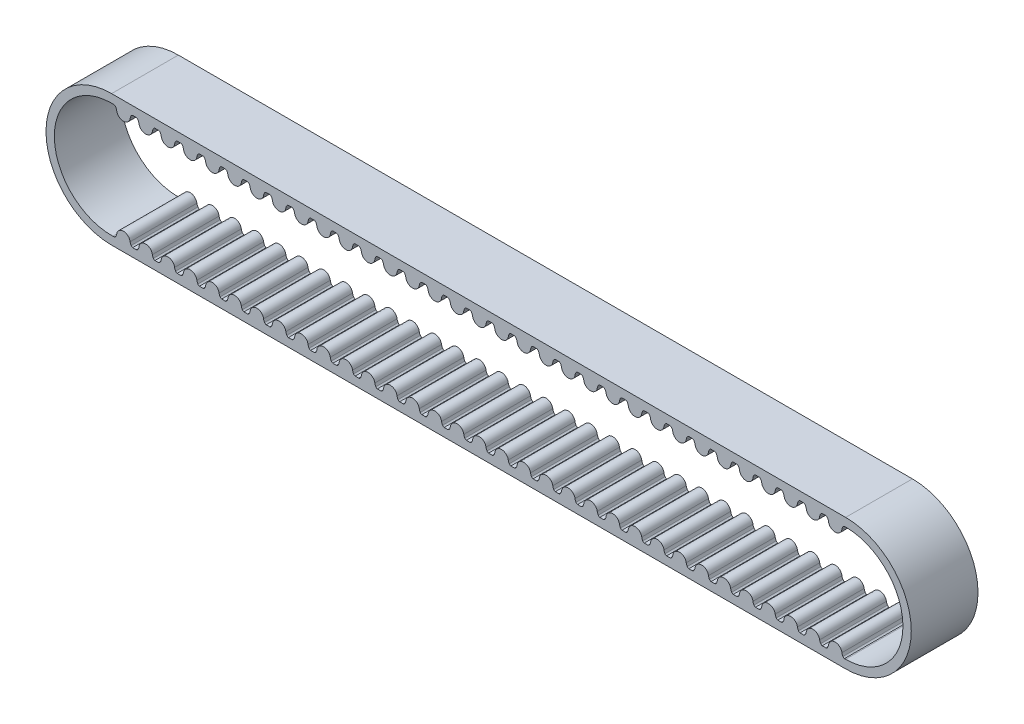
SolidWorks part; units mm, degrees
ref_plane "Front Plane" through (0, 0, 0) normal (0, 0, 1) x (1, 0, 0)
ref_plane "Top Plane" through (0, 0, 0) normal (0, 1, 0) x (1, 0, 0)
ref_plane "Right Plane" through (0, 0, 0) normal (1, 0, 0) x (0, 0, -1)
sketch "Sketch1" plane through (0, 0, 0) normal (0, 0, 1) x (1, 0, 0)
  line L0 (-149.0919, 9.0907) -> (-83.0919, 9.0907)
  line L1 (-148.8622, -1.9593) -> (-148.9877, -1.9593)
  line L2 (-148.8622, -1.9593) -> (-148.8621, -1.9593)
  line L3 (-146.8622, -1.9593) -> (-146.8621, -1.9593)
  line L4 (-147.1989, -1.9593) -> (-146.8622, -1.9593)
  line L5 (-145.1989, -1.9593) -> (-144.8622, -1.9593)
  line L6 (-144.8622, -1.9593) -> (-144.8621, -1.9593)
  line L7 (-143.1989, -1.9593) -> (-142.8622, -1.9593)
  line L8 (-142.8622, -1.9593) -> (-142.8621, -1.9593)
  line L9 (-141.1989, -1.9593) -> (-140.8622, -1.9593)
  line L10 (-140.8622, -1.9593) -> (-140.8621, -1.9593)
  line L11 (-139.1989, -1.9593) -> (-138.8622, -1.9593)
  line L12 (-138.8622, -1.9593) -> (-138.8621, -1.9593)
  line L13 (-137.1989, -1.9593) -> (-136.8622, -1.9593)
  line L14 (-136.8622, -1.9593) -> (-136.8621, -1.9593)
  line L15 (-135.1989, -1.9593) -> (-134.8622, -1.9593)
  line L16 (-134.8622, -1.9593) -> (-134.8621, -1.9593)
  line L17 (-133.1989, -1.9593) -> (-132.8622, -1.9593)
  line L18 (-132.8622, -1.9593) -> (-132.8621, -1.9593)
  line L19 (-131.1989, -1.9593) -> (-130.8622, -1.9593)
  line L20 (-130.8622, -1.9593) -> (-130.8621, -1.9593)
  line L21 (-129.1989, -1.9593) -> (-128.8622, -1.9593)
  line L22 (-128.8622, -1.9593) -> (-128.8621, -1.9593)
  line L23 (-127.1989, -1.9593) -> (-126.8622, -1.9593)
  line L24 (-126.8622, -1.9593) -> (-126.8621, -1.9593)
  line L25 (-125.1989, -1.9593) -> (-124.8622, -1.9593)
  line L26 (-124.8622, -1.9593) -> (-124.8621, -1.9593)
  line L27 (-123.1989, -1.9593) -> (-122.8622, -1.9593)
  line L28 (-122.8622, -1.9593) -> (-122.8621, -1.9593)
  line L29 (-121.1989, -1.9593) -> (-120.8622, -1.9593)
  line L30 (-120.8622, -1.9593) -> (-120.8621, -1.9593)
  line L31 (-119.1989, -1.9593) -> (-118.8622, -1.9593)
  line L32 (-118.8622, -1.9593) -> (-118.8621, -1.9593)
  line L33 (-117.1989, -1.9593) -> (-116.8622, -1.9593)
  line L34 (-116.8622, -1.9593) -> (-116.8621, -1.9593)
  line L35 (-115.1989, -1.9593) -> (-114.8622, -1.9593)
  line L36 (-114.8622, -1.9593) -> (-114.8621, -1.9593)
  line L37 (-113.1989, -1.9593) -> (-112.8622, -1.9593)
  line L38 (-112.8622, -1.9593) -> (-112.8621, -1.9593)
  line L39 (-111.1989, -1.9593) -> (-110.8622, -1.9593)
  line L40 (-110.8622, -1.9593) -> (-110.8621, -1.9593)
  line L41 (-109.1989, -1.9593) -> (-108.8622, -1.9593)
  line L42 (-108.8622, -1.9593) -> (-108.8621, -1.9593)
  line L43 (-107.1989, -1.9593) -> (-106.8622, -1.9593)
  line L44 (-106.8622, -1.9593) -> (-106.8621, -1.9593)
  line L45 (-105.1989, -1.9593) -> (-104.8622, -1.9593)
  line L46 (-104.8622, -1.9593) -> (-104.8621, -1.9593)
  line L47 (-103.1989, -1.9593) -> (-102.8622, -1.9593)
  line L48 (-102.8622, -1.9593) -> (-102.8621, -1.9593)
  line L49 (-101.1989, -1.9593) -> (-100.8622, -1.9593)
  line L50 (-100.8622, -1.9593) -> (-100.8621, -1.9593)
  line L51 (-99.1989, -1.9593) -> (-98.8622, -1.9593)
  line L52 (-98.8622, -1.9593) -> (-98.8621, -1.9593)
  line L53 (-97.1989, -1.9593) -> (-96.8622, -1.9593)
  line L54 (-96.8622, -1.9593) -> (-96.8621, -1.9593)
  line L55 (-95.1989, -1.9593) -> (-94.8622, -1.9593)
  line L56 (-94.8622, -1.9593) -> (-94.8621, -1.9593)
  line L57 (-93.1989, -1.9593) -> (-92.8622, -1.9593)
  line L58 (-92.8622, -1.9593) -> (-92.8621, -1.9593)
  line L59 (-91.1989, -1.9593) -> (-90.8622, -1.9593)
  line L60 (-90.8622, -1.9593) -> (-90.8621, -1.9593)
  line L61 (-89.1989, -1.9593) -> (-88.8622, -1.9593)
  line L62 (-88.8622, -1.9593) -> (-88.8621, -1.9593)
  line L63 (-87.1989, -1.9593) -> (-86.8622, -1.9593)
  line L64 (-86.8622, -1.9593) -> (-86.8621, -1.9593)
  line L65 (-85.1989, -1.9593) -> (-84.8622, -1.9593)
  line L66 (-84.8622, -1.9593) -> (-84.8621, -1.9593)
  line L277 (-83.0919, 3.1907) -> (-46.1296, 3.1907) construction
  line L278 (-83.1989, 8.3407) -> (-83.0919, 8.3407)
  line L279 (-149.0919, -2.7093) -> (-83.0919, -2.7093)
  line L280 (-149.1969, 8.3407) -> (-148.8622, 8.3407)
  line L491 (-84.8622, 8.3407) -> (-84.8621, 8.3407)
  line L492 (-85.1989, 8.3407) -> (-84.8622, 8.3407)
  line L493 (-86.8622, 8.3407) -> (-86.8621, 8.3407)
  line L494 (-87.1989, 8.3407) -> (-86.8622, 8.3407)
  line L495 (-88.8622, 8.3407) -> (-88.8621, 8.3407)
  line L496 (-89.1989, 8.3407) -> (-88.8622, 8.3407)
  line L497 (-90.8622, 8.3407) -> (-90.8621, 8.3407)
  line L498 (-91.1989, 8.3407) -> (-90.8622, 8.3407)
  line L499 (-92.8622, 8.3407) -> (-92.8621, 8.3407)
  line L500 (-93.1989, 8.3407) -> (-92.8622, 8.3407)
  line L501 (-94.8622, 8.3407) -> (-94.8621, 8.3407)
  line L502 (-95.1989, 8.3407) -> (-94.8622, 8.3407)
  line L503 (-96.8622, 8.3407) -> (-96.8621, 8.3407)
  line L504 (-97.1989, 8.3407) -> (-96.8622, 8.3407)
  line L505 (-98.8622, 8.3407) -> (-98.8621, 8.3407)
  line L506 (-99.1989, 8.3407) -> (-98.8622, 8.3407)
  line L507 (-100.8622, 8.3407) -> (-100.8621, 8.3407)
  line L508 (-101.1989, 8.3407) -> (-100.8622, 8.3407)
  line L509 (-102.8622, 8.3407) -> (-102.8621, 8.3407)
  line L510 (-103.1989, 8.3407) -> (-102.8622, 8.3407)
  line L511 (-104.8622, 8.3407) -> (-104.8621, 8.3407)
  line L512 (-105.1989, 8.3407) -> (-104.8622, 8.3407)
  line L513 (-106.8622, 8.3407) -> (-106.8621, 8.3407)
  line L514 (-107.1989, 8.3407) -> (-106.8622, 8.3407)
  line L515 (-108.8622, 8.3407) -> (-108.8621, 8.3407)
  line L516 (-109.1989, 8.3407) -> (-108.8622, 8.3407)
  line L517 (-110.8622, 8.3407) -> (-110.8621, 8.3407)
  line L518 (-111.1989, 8.3407) -> (-110.8622, 8.3407)
  line L519 (-112.8622, 8.3407) -> (-112.8621, 8.3407)
  line L520 (-113.1989, 8.3407) -> (-112.8622, 8.3407)
  line L521 (-114.8622, 8.3407) -> (-114.8621, 8.3407)
  line L522 (-115.1989, 8.3407) -> (-114.8622, 8.3407)
  line L523 (-116.8622, 8.3407) -> (-116.8621, 8.3407)
  line L524 (-117.1989, 8.3407) -> (-116.8622, 8.3407)
  line L525 (-118.8622, 8.3407) -> (-118.8621, 8.3407)
  line L526 (-119.1989, 8.3407) -> (-118.8622, 8.3407)
  line L527 (-120.8622, 8.3407) -> (-120.8621, 8.3407)
  line L528 (-121.1989, 8.3407) -> (-120.8622, 8.3407)
  line L529 (-122.8622, 8.3407) -> (-122.8621, 8.3407)
  line L530 (-123.1989, 8.3407) -> (-122.8622, 8.3407)
  line L531 (-124.8622, 8.3407) -> (-124.8621, 8.3407)
  line L532 (-125.1989, 8.3407) -> (-124.8622, 8.3407)
  line L533 (-126.8622, 8.3407) -> (-126.8621, 8.3407)
  line L534 (-127.1989, 8.3407) -> (-126.8622, 8.3407)
  line L535 (-128.8622, 8.3407) -> (-128.8621, 8.3407)
  line L536 (-129.1989, 8.3407) -> (-128.8622, 8.3407)
  line L537 (-130.8622, 8.3407) -> (-130.8621, 8.3407)
  line L538 (-131.1989, 8.3407) -> (-130.8622, 8.3407)
  line L539 (-132.8622, 8.3407) -> (-132.8621, 8.3407)
  line L540 (-133.1989, 8.3407) -> (-132.8622, 8.3407)
  line L541 (-134.8622, 8.3407) -> (-134.8621, 8.3407)
  line L542 (-135.1989, 8.3407) -> (-134.8622, 8.3407)
  line L543 (-136.8622, 8.3407) -> (-136.8621, 8.3407)
  line L544 (-137.1989, 8.3407) -> (-136.8622, 8.3407)
  line L545 (-138.8622, 8.3407) -> (-138.8621, 8.3407)
  line L546 (-139.1989, 8.3407) -> (-138.8622, 8.3407)
  line L547 (-140.8622, 8.3407) -> (-140.8621, 8.3407)
  line L548 (-141.1989, 8.3407) -> (-140.8622, 8.3407)
  line L549 (-142.8622, 8.3407) -> (-142.8621, 8.3407)
  line L550 (-143.1989, 8.3407) -> (-142.8622, 8.3407)
  line L551 (-144.8622, 8.3407) -> (-144.8621, 8.3407)
  line L552 (-145.1989, 8.3407) -> (-144.8622, 8.3407)
  line L553 (-147.1989, 8.3407) -> (-146.8622, 8.3407)
  line L554 (-146.8622, 8.3407) -> (-146.8621, 8.3407)
  line L555 (-148.8622, 8.3407) -> (-148.8621, 8.3407)
  line L556 (-83.1989, -1.9593) -> (-83.0919, -1.9593)
  arc A0 (-149.1969, 8.3407) -> (-148.9869, -1.9593) centre (-149.0919, 3.1907) ccw
  arc A1 (-83.0919, -1.9593) -> (-83.0919, 8.3407) centre (-83.0919, 3.1907) ccw
  arc A2 (-146.8621, -1.9593) -> (-146.7228, -1.8564) centre (-146.9197, -1.7354) ccw
  arc A3 (-148.8621, -1.9593) -> (-148.7228, -1.8564) centre (-148.9197, -1.7354) ccw
  arc A4 (-148.7228, -1.8564) -> (-148.6336, -1.611) centre (-149.2769, -1.5162) ccw
  arc A5 (-147.4274, -1.611) -> (-148.6336, -1.611) centre (-148.0305, -1.6999) ccw
  arc A6 (-147.4274, -1.611) -> (-147.3383, -1.8564) centre (-146.7842, -1.5162) ccw
  arc A7 (-147.3383, -1.8564) -> (-147.1989, -1.9593) centre (-147.1413, -1.7354) ccw
  arc A8 (-146.7228, -1.8564) -> (-146.6336, -1.611) centre (-147.2769, -1.5162) ccw
  arc A9 (-145.4274, -1.611) -> (-146.6336, -1.611) centre (-146.0305, -1.6999) ccw
  arc A10 (-145.4274, -1.611) -> (-145.3383, -1.8564) centre (-144.7842, -1.5162) ccw
  arc A11 (-145.3383, -1.8564) -> (-145.1989, -1.9593) centre (-145.1413, -1.7354) ccw
  arc A12 (-144.8621, -1.9593) -> (-144.7228, -1.8564) centre (-144.9197, -1.7354) ccw
  arc A13 (-144.7228, -1.8564) -> (-144.6336, -1.611) centre (-145.2769, -1.5162) ccw
  arc A14 (-143.4274, -1.611) -> (-144.6336, -1.611) centre (-144.0305, -1.6999) ccw
  arc A15 (-143.4274, -1.611) -> (-143.3383, -1.8564) centre (-142.7842, -1.5162) ccw
  arc A16 (-143.3383, -1.8564) -> (-143.1989, -1.9593) centre (-143.1413, -1.7354) ccw
  arc A17 (-142.8621, -1.9593) -> (-142.7228, -1.8564) centre (-142.9197, -1.7354) ccw
  arc A18 (-142.7228, -1.8564) -> (-142.6336, -1.611) centre (-143.2769, -1.5162) ccw
  arc A19 (-141.4274, -1.611) -> (-142.6336, -1.611) centre (-142.0305, -1.6999) ccw
  arc A20 (-141.4274, -1.611) -> (-141.3383, -1.8564) centre (-140.7842, -1.5162) ccw
  arc A21 (-141.3383, -1.8564) -> (-141.1989, -1.9593) centre (-141.1413, -1.7354) ccw
  arc A22 (-140.8621, -1.9593) -> (-140.7228, -1.8564) centre (-140.9197, -1.7354) ccw
  arc A23 (-140.7228, -1.8564) -> (-140.6336, -1.611) centre (-141.2769, -1.5162) ccw
  arc A24 (-139.4274, -1.611) -> (-140.6336, -1.611) centre (-140.0305, -1.6999) ccw
  arc A25 (-139.4274, -1.611) -> (-139.3383, -1.8564) centre (-138.7842, -1.5162) ccw
  arc A26 (-139.3383, -1.8564) -> (-139.1989, -1.9593) centre (-139.1413, -1.7354) ccw
  arc A27 (-138.8621, -1.9593) -> (-138.7228, -1.8564) centre (-138.9197, -1.7354) ccw
  arc A28 (-138.7228, -1.8564) -> (-138.6336, -1.611) centre (-139.2769, -1.5162) ccw
  arc A29 (-137.4274, -1.611) -> (-138.6336, -1.611) centre (-138.0305, -1.6999) ccw
  arc A30 (-137.4274, -1.611) -> (-137.3383, -1.8564) centre (-136.7842, -1.5162) ccw
  arc A31 (-137.3383, -1.8564) -> (-137.1989, -1.9593) centre (-137.1413, -1.7354) ccw
  arc A32 (-136.8621, -1.9593) -> (-136.7228, -1.8564) centre (-136.9197, -1.7354) ccw
  arc A33 (-136.7228, -1.8564) -> (-136.6336, -1.611) centre (-137.2769, -1.5162) ccw
  arc A34 (-135.4274, -1.611) -> (-136.6336, -1.611) centre (-136.0305, -1.6999) ccw
  arc A35 (-135.4274, -1.611) -> (-135.3383, -1.8564) centre (-134.7842, -1.5162) ccw
  arc A36 (-135.3383, -1.8564) -> (-135.1989, -1.9593) centre (-135.1413, -1.7354) ccw
  arc A37 (-134.8621, -1.9593) -> (-134.7228, -1.8564) centre (-134.9197, -1.7354) ccw
  arc A38 (-134.7228, -1.8564) -> (-134.6336, -1.611) centre (-135.2769, -1.5162) ccw
  arc A39 (-133.4274, -1.611) -> (-134.6336, -1.611) centre (-134.0305, -1.6999) ccw
  arc A40 (-133.4274, -1.611) -> (-133.3383, -1.8564) centre (-132.7842, -1.5162) ccw
  arc A41 (-133.3383, -1.8564) -> (-133.1989, -1.9593) centre (-133.1413, -1.7354) ccw
  arc A42 (-132.8621, -1.9593) -> (-132.7228, -1.8564) centre (-132.9197, -1.7354) ccw
  arc A43 (-132.7228, -1.8564) -> (-132.6336, -1.611) centre (-133.2769, -1.5162) ccw
  arc A44 (-131.4274, -1.611) -> (-132.6336, -1.611) centre (-132.0305, -1.6999) ccw
  arc A45 (-131.4274, -1.611) -> (-131.3383, -1.8564) centre (-130.7842, -1.5162) ccw
  arc A46 (-131.3383, -1.8564) -> (-131.1989, -1.9593) centre (-131.1413, -1.7354) ccw
  arc A47 (-130.8621, -1.9593) -> (-130.7228, -1.8564) centre (-130.9197, -1.7354) ccw
  arc A48 (-130.7228, -1.8564) -> (-130.6336, -1.611) centre (-131.2769, -1.5162) ccw
  arc A49 (-129.4274, -1.611) -> (-130.6336, -1.611) centre (-130.0305, -1.6999) ccw
  arc A50 (-129.4274, -1.611) -> (-129.3383, -1.8564) centre (-128.7842, -1.5162) ccw
  arc A51 (-129.3383, -1.8564) -> (-129.1989, -1.9593) centre (-129.1413, -1.7354) ccw
  arc A52 (-128.8621, -1.9593) -> (-128.7228, -1.8564) centre (-128.9197, -1.7354) ccw
  arc A53 (-128.7228, -1.8564) -> (-128.6336, -1.611) centre (-129.2769, -1.5162) ccw
  arc A54 (-127.4274, -1.611) -> (-128.6336, -1.611) centre (-128.0305, -1.6999) ccw
  arc A55 (-127.4274, -1.611) -> (-127.3383, -1.8564) centre (-126.7842, -1.5162) ccw
  arc A56 (-127.3383, -1.8564) -> (-127.1989, -1.9593) centre (-127.1413, -1.7354) ccw
  arc A57 (-126.8621, -1.9593) -> (-126.7228, -1.8564) centre (-126.9197, -1.7354) ccw
  arc A58 (-126.7228, -1.8564) -> (-126.6336, -1.611) centre (-127.2769, -1.5162) ccw
  arc A59 (-125.4274, -1.611) -> (-126.6336, -1.611) centre (-126.0305, -1.6999) ccw
  arc A60 (-125.4274, -1.611) -> (-125.3383, -1.8564) centre (-124.7842, -1.5162) ccw
  arc A61 (-125.3383, -1.8564) -> (-125.1989, -1.9593) centre (-125.1413, -1.7354) ccw
  arc A62 (-124.8621, -1.9593) -> (-124.7228, -1.8564) centre (-124.9197, -1.7354) ccw
  arc A63 (-124.7228, -1.8564) -> (-124.6336, -1.611) centre (-125.2769, -1.5162) ccw
  arc A64 (-123.4274, -1.611) -> (-124.6336, -1.611) centre (-124.0305, -1.6999) ccw
  arc A65 (-123.4274, -1.611) -> (-123.3383, -1.8564) centre (-122.7842, -1.5162) ccw
  arc A66 (-123.3383, -1.8564) -> (-123.1989, -1.9593) centre (-123.1413, -1.7354) ccw
  arc A67 (-122.8621, -1.9593) -> (-122.7228, -1.8564) centre (-122.9197, -1.7354) ccw
  arc A68 (-122.7228, -1.8564) -> (-122.6336, -1.611) centre (-123.2769, -1.5162) ccw
  arc A69 (-121.4274, -1.611) -> (-122.6336, -1.611) centre (-122.0305, -1.6999) ccw
  arc A70 (-121.4274, -1.611) -> (-121.3383, -1.8564) centre (-120.7842, -1.5162) ccw
  arc A71 (-121.3383, -1.8564) -> (-121.1989, -1.9593) centre (-121.1413, -1.7354) ccw
  arc A72 (-120.8621, -1.9593) -> (-120.7228, -1.8564) centre (-120.9197, -1.7354) ccw
  arc A73 (-120.7228, -1.8564) -> (-120.6336, -1.611) centre (-121.2769, -1.5162) ccw
  arc A74 (-119.4274, -1.611) -> (-120.6336, -1.611) centre (-120.0305, -1.6999) ccw
  arc A75 (-119.4274, -1.611) -> (-119.3383, -1.8564) centre (-118.7842, -1.5162) ccw
  arc A76 (-119.3383, -1.8564) -> (-119.1989, -1.9593) centre (-119.1413, -1.7354) ccw
  arc A77 (-118.8621, -1.9593) -> (-118.7228, -1.8564) centre (-118.9197, -1.7354) ccw
  arc A78 (-118.7228, -1.8564) -> (-118.6336, -1.611) centre (-119.2769, -1.5162) ccw
  arc A79 (-117.4274, -1.611) -> (-118.6336, -1.611) centre (-118.0305, -1.6999) ccw
  arc A80 (-117.4274, -1.611) -> (-117.3383, -1.8564) centre (-116.7842, -1.5162) ccw
  arc A81 (-117.3383, -1.8564) -> (-117.1989, -1.9593) centre (-117.1413, -1.7354) ccw
  arc A82 (-116.8621, -1.9593) -> (-116.7228, -1.8564) centre (-116.9197, -1.7354) ccw
  arc A83 (-116.7228, -1.8564) -> (-116.6336, -1.611) centre (-117.2769, -1.5162) ccw
  arc A84 (-115.4274, -1.611) -> (-116.6336, -1.611) centre (-116.0305, -1.6999) ccw
  arc A85 (-115.4274, -1.611) -> (-115.3383, -1.8564) centre (-114.7842, -1.5162) ccw
  arc A86 (-115.3383, -1.8564) -> (-115.1989, -1.9593) centre (-115.1413, -1.7354) ccw
  arc A87 (-114.8621, -1.9593) -> (-114.7228, -1.8564) centre (-114.9197, -1.7354) ccw
  arc A88 (-114.7228, -1.8564) -> (-114.6336, -1.611) centre (-115.2769, -1.5162) ccw
  arc A89 (-113.4274, -1.611) -> (-114.6336, -1.611) centre (-114.0305, -1.6999) ccw
  arc A90 (-113.4274, -1.611) -> (-113.3383, -1.8564) centre (-112.7842, -1.5162) ccw
  arc A91 (-113.3383, -1.8564) -> (-113.1989, -1.9593) centre (-113.1413, -1.7354) ccw
  arc A92 (-112.8621, -1.9593) -> (-112.7228, -1.8564) centre (-112.9197, -1.7354) ccw
  arc A93 (-112.7228, -1.8564) -> (-112.6336, -1.611) centre (-113.2769, -1.5162) ccw
  arc A94 (-111.4274, -1.611) -> (-112.6336, -1.611) centre (-112.0305, -1.6999) ccw
  arc A95 (-111.4274, -1.611) -> (-111.3383, -1.8564) centre (-110.7842, -1.5162) ccw
  arc A96 (-111.3383, -1.8564) -> (-111.1989, -1.9593) centre (-111.1413, -1.7354) ccw
  arc A97 (-110.8621, -1.9593) -> (-110.7228, -1.8564) centre (-110.9197, -1.7354) ccw
  arc A98 (-110.7228, -1.8564) -> (-110.6336, -1.611) centre (-111.2769, -1.5162) ccw
  arc A99 (-109.4274, -1.611) -> (-110.6336, -1.611) centre (-110.0305, -1.6999) ccw
  arc A100 (-109.4274, -1.611) -> (-109.3383, -1.8564) centre (-108.7842, -1.5162) ccw
  arc A101 (-109.3383, -1.8564) -> (-109.1989, -1.9593) centre (-109.1413, -1.7354) ccw
  arc A102 (-108.8621, -1.9593) -> (-108.7228, -1.8564) centre (-108.9197, -1.7354) ccw
  arc A103 (-108.7228, -1.8564) -> (-108.6336, -1.611) centre (-109.2769, -1.5162) ccw
  arc A104 (-107.4274, -1.611) -> (-108.6336, -1.611) centre (-108.0305, -1.6999) ccw
  arc A105 (-107.4274, -1.611) -> (-107.3383, -1.8564) centre (-106.7842, -1.5162) ccw
  arc A106 (-107.3383, -1.8564) -> (-107.1989, -1.9593) centre (-107.1413, -1.7354) ccw
  arc A107 (-106.8621, -1.9593) -> (-106.7228, -1.8564) centre (-106.9197, -1.7354) ccw
  arc A108 (-106.7228, -1.8564) -> (-106.6336, -1.611) centre (-107.2769, -1.5162) ccw
  arc A109 (-105.4274, -1.611) -> (-106.6336, -1.611) centre (-106.0305, -1.6999) ccw
  arc A110 (-105.4274, -1.611) -> (-105.3383, -1.8564) centre (-104.7842, -1.5162) ccw
  arc A111 (-105.3383, -1.8564) -> (-105.1989, -1.9593) centre (-105.1413, -1.7354) ccw
  arc A112 (-104.8621, -1.9593) -> (-104.7228, -1.8564) centre (-104.9197, -1.7354) ccw
  arc A113 (-104.7228, -1.8564) -> (-104.6336, -1.611) centre (-105.2769, -1.5162) ccw
  arc A114 (-103.4274, -1.611) -> (-104.6336, -1.611) centre (-104.0305, -1.6999) ccw
  arc A115 (-103.4274, -1.611) -> (-103.3383, -1.8564) centre (-102.7842, -1.5162) ccw
  arc A116 (-103.3383, -1.8564) -> (-103.1989, -1.9593) centre (-103.1413, -1.7354) ccw
  arc A117 (-102.8621, -1.9593) -> (-102.7228, -1.8564) centre (-102.9197, -1.7354) ccw
  arc A118 (-102.7228, -1.8564) -> (-102.6336, -1.611) centre (-103.2769, -1.5162) ccw
  arc A119 (-101.4274, -1.611) -> (-102.6336, -1.611) centre (-102.0305, -1.6999) ccw
  arc A120 (-101.4274, -1.611) -> (-101.3383, -1.8564) centre (-100.7842, -1.5162) ccw
  arc A121 (-101.3383, -1.8564) -> (-101.1989, -1.9593) centre (-101.1413, -1.7354) ccw
  arc A122 (-100.8621, -1.9593) -> (-100.7228, -1.8564) centre (-100.9197, -1.7354) ccw
  arc A123 (-100.7228, -1.8564) -> (-100.6336, -1.611) centre (-101.2769, -1.5162) ccw
  arc A124 (-99.4274, -1.611) -> (-100.6336, -1.611) centre (-100.0305, -1.6999) ccw
  arc A125 (-99.4274, -1.611) -> (-99.3383, -1.8564) centre (-98.7842, -1.5162) ccw
  arc A126 (-99.3383, -1.8564) -> (-99.1989, -1.9593) centre (-99.1413, -1.7354) ccw
  arc A127 (-98.8621, -1.9593) -> (-98.7228, -1.8564) centre (-98.9197, -1.7354) ccw
  arc A128 (-98.7228, -1.8564) -> (-98.6336, -1.611) centre (-99.2769, -1.5162) ccw
  arc A129 (-97.4274, -1.611) -> (-98.6336, -1.611) centre (-98.0305, -1.6999) ccw
  arc A130 (-97.4274, -1.611) -> (-97.3383, -1.8564) centre (-96.7842, -1.5162) ccw
  arc A131 (-97.3383, -1.8564) -> (-97.1989, -1.9593) centre (-97.1413, -1.7354) ccw
  arc A132 (-96.8621, -1.9593) -> (-96.7228, -1.8564) centre (-96.9197, -1.7354) ccw
  arc A133 (-96.7228, -1.8564) -> (-96.6336, -1.611) centre (-97.2769, -1.5162) ccw
  arc A134 (-95.4274, -1.611) -> (-96.6336, -1.611) centre (-96.0305, -1.6999) ccw
  arc A135 (-95.4274, -1.611) -> (-95.3383, -1.8564) centre (-94.7842, -1.5162) ccw
  arc A136 (-95.3383, -1.8564) -> (-95.1989, -1.9593) centre (-95.1413, -1.7354) ccw
  arc A137 (-94.8621, -1.9593) -> (-94.7228, -1.8564) centre (-94.9197, -1.7354) ccw
  arc A138 (-94.7228, -1.8564) -> (-94.6336, -1.611) centre (-95.2769, -1.5162) ccw
  arc A139 (-93.4274, -1.611) -> (-94.6336, -1.611) centre (-94.0305, -1.6999) ccw
  arc A140 (-93.4274, -1.611) -> (-93.3383, -1.8564) centre (-92.7842, -1.5162) ccw
  arc A141 (-93.3383, -1.8564) -> (-93.1989, -1.9593) centre (-93.1413, -1.7354) ccw
  arc A142 (-92.8621, -1.9593) -> (-92.7228, -1.8564) centre (-92.9197, -1.7354) ccw
  arc A143 (-92.7228, -1.8564) -> (-92.6336, -1.611) centre (-93.2769, -1.5162) ccw
  arc A144 (-91.4274, -1.611) -> (-92.6336, -1.611) centre (-92.0305, -1.6999) ccw
  arc A145 (-91.4274, -1.611) -> (-91.3383, -1.8564) centre (-90.7842, -1.5162) ccw
  arc A146 (-91.3383, -1.8564) -> (-91.1989, -1.9593) centre (-91.1413, -1.7354) ccw
  arc A147 (-90.8621, -1.9593) -> (-90.7228, -1.8564) centre (-90.9197, -1.7354) ccw
  arc A148 (-90.7228, -1.8564) -> (-90.6336, -1.611) centre (-91.2769, -1.5162) ccw
  arc A149 (-89.4274, -1.611) -> (-90.6336, -1.611) centre (-90.0305, -1.6999) ccw
  arc A150 (-89.4274, -1.611) -> (-89.3383, -1.8564) centre (-88.7842, -1.5162) ccw
  arc A151 (-89.3383, -1.8564) -> (-89.1989, -1.9593) centre (-89.1413, -1.7354) ccw
  arc A152 (-88.8621, -1.9593) -> (-88.7228, -1.8564) centre (-88.9197, -1.7354) ccw
  arc A153 (-88.7228, -1.8564) -> (-88.6336, -1.611) centre (-89.2769, -1.5162) ccw
  arc A154 (-87.4274, -1.611) -> (-88.6336, -1.611) centre (-88.0305, -1.6999) ccw
  arc A155 (-87.4274, -1.611) -> (-87.3383, -1.8564) centre (-86.7842, -1.5162) ccw
  arc A156 (-87.3383, -1.8564) -> (-87.1989, -1.9593) centre (-87.1413, -1.7354) ccw
  arc A157 (-86.8621, -1.9593) -> (-86.7228, -1.8564) centre (-86.9197, -1.7354) ccw
  arc A158 (-86.7228, -1.8564) -> (-86.6336, -1.611) centre (-87.2769, -1.5162) ccw
  arc A159 (-85.4274, -1.611) -> (-86.6336, -1.611) centre (-86.0305, -1.6999) ccw
  arc A160 (-85.4274, -1.611) -> (-85.3383, -1.8564) centre (-84.7842, -1.5162) ccw
  arc A161 (-85.3383, -1.8564) -> (-85.1989, -1.9593) centre (-85.1413, -1.7354) ccw
  arc A162 (-84.8621, -1.9593) -> (-84.7228, -1.8564) centre (-84.9197, -1.7354) ccw
  arc A163 (-84.7228, -1.8564) -> (-84.6336, -1.611) centre (-85.2769, -1.5162) ccw
  arc A164 (-83.4274, -1.611) -> (-84.6336, -1.611) centre (-84.0305, -1.6999) ccw
  arc A165 (-83.4274, -1.611) -> (-83.3383, -1.8564) centre (-82.7842, -1.5162) ccw
  arc A166 (-83.3383, -1.8564) -> (-83.1989, -1.9593) centre (-83.1413, -1.7354) ccw
  arc A692 (-149.0919, 9.0907) -> (-149.0919, -2.7093) centre (-149.0919, 3.1907) ccw
  arc A693 (-83.0919, -2.7093) -> (-83.0919, 9.0907) centre (-83.0919, 3.1907) ccw
  arc A1219 (-83.3383, 8.2378) -> (-83.1989, 8.3407) centre (-83.1413, 8.1169) cw
  arc A1220 (-83.4274, 7.9924) -> (-83.3383, 8.2378) centre (-82.7842, 7.8976) cw
  arc A1221 (-83.4274, 7.9924) -> (-84.6336, 7.9924) centre (-84.0305, 8.0813) cw
  arc A1222 (-84.7228, 8.2378) -> (-84.6336, 7.9924) centre (-85.2769, 7.8976) cw
  arc A1223 (-84.8621, 8.3407) -> (-84.7228, 8.2378) centre (-84.9197, 8.1169) cw
  arc A1224 (-85.3383, 8.2378) -> (-85.1989, 8.3407) centre (-85.1413, 8.1169) cw
  arc A1225 (-85.4274, 7.9924) -> (-85.3383, 8.2378) centre (-84.7842, 7.8976) cw
  arc A1226 (-85.4274, 7.9924) -> (-86.6336, 7.9924) centre (-86.0305, 8.0813) cw
  arc A1227 (-86.7228, 8.2378) -> (-86.6336, 7.9924) centre (-87.2769, 7.8976) cw
  arc A1228 (-86.8621, 8.3407) -> (-86.7228, 8.2378) centre (-86.9197, 8.1169) cw
  arc A1229 (-87.3383, 8.2378) -> (-87.1989, 8.3407) centre (-87.1413, 8.1169) cw
  arc A1230 (-87.4274, 7.9924) -> (-87.3383, 8.2378) centre (-86.7842, 7.8976) cw
  arc A1231 (-87.4274, 7.9924) -> (-88.6336, 7.9924) centre (-88.0305, 8.0813) cw
  arc A1232 (-88.7228, 8.2378) -> (-88.6336, 7.9924) centre (-89.2769, 7.8976) cw
  arc A1233 (-88.8621, 8.3407) -> (-88.7228, 8.2378) centre (-88.9197, 8.1169) cw
  arc A1234 (-89.3383, 8.2378) -> (-89.1989, 8.3407) centre (-89.1413, 8.1169) cw
  arc A1235 (-89.4274, 7.9924) -> (-89.3383, 8.2378) centre (-88.7842, 7.8976) cw
  arc A1236 (-89.4274, 7.9924) -> (-90.6336, 7.9924) centre (-90.0305, 8.0813) cw
  arc A1237 (-90.7228, 8.2378) -> (-90.6336, 7.9924) centre (-91.2769, 7.8976) cw
  arc A1238 (-90.8621, 8.3407) -> (-90.7228, 8.2378) centre (-90.9197, 8.1169) cw
  arc A1239 (-91.3383, 8.2378) -> (-91.1989, 8.3407) centre (-91.1413, 8.1169) cw
  arc A1240 (-91.4274, 7.9924) -> (-91.3383, 8.2378) centre (-90.7842, 7.8976) cw
  arc A1241 (-91.4274, 7.9924) -> (-92.6336, 7.9924) centre (-92.0305, 8.0813) cw
  arc A1242 (-92.7228, 8.2378) -> (-92.6336, 7.9924) centre (-93.2769, 7.8976) cw
  arc A1243 (-92.8621, 8.3407) -> (-92.7228, 8.2378) centre (-92.9197, 8.1169) cw
  arc A1244 (-93.3383, 8.2378) -> (-93.1989, 8.3407) centre (-93.1413, 8.1169) cw
  arc A1245 (-93.4274, 7.9924) -> (-93.3383, 8.2378) centre (-92.7842, 7.8976) cw
  arc A1246 (-93.4274, 7.9924) -> (-94.6336, 7.9924) centre (-94.0305, 8.0813) cw
  arc A1247 (-94.7228, 8.2378) -> (-94.6336, 7.9924) centre (-95.2769, 7.8976) cw
  arc A1248 (-94.8621, 8.3407) -> (-94.7228, 8.2378) centre (-94.9197, 8.1169) cw
  arc A1249 (-95.3383, 8.2378) -> (-95.1989, 8.3407) centre (-95.1413, 8.1169) cw
  arc A1250 (-95.4274, 7.9924) -> (-95.3383, 8.2378) centre (-94.7842, 7.8976) cw
  arc A1251 (-95.4274, 7.9924) -> (-96.6336, 7.9924) centre (-96.0305, 8.0813) cw
  arc A1252 (-96.7228, 8.2378) -> (-96.6336, 7.9924) centre (-97.2769, 7.8976) cw
  arc A1253 (-96.8621, 8.3407) -> (-96.7228, 8.2378) centre (-96.9197, 8.1169) cw
  arc A1254 (-97.3383, 8.2378) -> (-97.1989, 8.3407) centre (-97.1413, 8.1169) cw
  arc A1255 (-97.4274, 7.9924) -> (-97.3383, 8.2378) centre (-96.7842, 7.8976) cw
  arc A1256 (-97.4274, 7.9924) -> (-98.6336, 7.9924) centre (-98.0305, 8.0813) cw
  arc A1257 (-98.7228, 8.2378) -> (-98.6336, 7.9924) centre (-99.2769, 7.8976) cw
  arc A1258 (-98.8621, 8.3407) -> (-98.7228, 8.2378) centre (-98.9197, 8.1169) cw
  arc A1259 (-99.3383, 8.2378) -> (-99.1989, 8.3407) centre (-99.1413, 8.1169) cw
  arc A1260 (-99.4274, 7.9924) -> (-99.3383, 8.2378) centre (-98.7842, 7.8976) cw
  arc A1261 (-99.4274, 7.9924) -> (-100.6336, 7.9924) centre (-100.0305, 8.0813) cw
  arc A1262 (-100.7228, 8.2378) -> (-100.6336, 7.9924) centre (-101.2769, 7.8976) cw
  arc A1263 (-100.8621, 8.3407) -> (-100.7228, 8.2378) centre (-100.9197, 8.1169) cw
  arc A1264 (-101.3383, 8.2378) -> (-101.1989, 8.3407) centre (-101.1413, 8.1169) cw
  arc A1265 (-101.4274, 7.9924) -> (-101.3383, 8.2378) centre (-100.7842, 7.8976) cw
  arc A1266 (-101.4274, 7.9924) -> (-102.6336, 7.9924) centre (-102.0305, 8.0813) cw
  arc A1267 (-102.7228, 8.2378) -> (-102.6336, 7.9924) centre (-103.2769, 7.8976) cw
  arc A1268 (-102.8621, 8.3407) -> (-102.7228, 8.2378) centre (-102.9197, 8.1169) cw
  arc A1269 (-103.3383, 8.2378) -> (-103.1989, 8.3407) centre (-103.1413, 8.1169) cw
  arc A1270 (-103.4274, 7.9924) -> (-103.3383, 8.2378) centre (-102.7842, 7.8976) cw
  arc A1271 (-103.4274, 7.9924) -> (-104.6336, 7.9924) centre (-104.0305, 8.0813) cw
  arc A1272 (-104.7228, 8.2378) -> (-104.6336, 7.9924) centre (-105.2769, 7.8976) cw
  arc A1273 (-104.8621, 8.3407) -> (-104.7228, 8.2378) centre (-104.9197, 8.1169) cw
  arc A1274 (-105.3383, 8.2378) -> (-105.1989, 8.3407) centre (-105.1413, 8.1169) cw
  arc A1275 (-105.4274, 7.9924) -> (-105.3383, 8.2378) centre (-104.7842, 7.8976) cw
  arc A1276 (-105.4274, 7.9924) -> (-106.6336, 7.9924) centre (-106.0305, 8.0813) cw
  arc A1277 (-106.7228, 8.2378) -> (-106.6336, 7.9924) centre (-107.2769, 7.8976) cw
  arc A1278 (-106.8621, 8.3407) -> (-106.7228, 8.2378) centre (-106.9197, 8.1169) cw
  arc A1279 (-107.3383, 8.2378) -> (-107.1989, 8.3407) centre (-107.1413, 8.1169) cw
  arc A1280 (-107.4274, 7.9924) -> (-107.3383, 8.2378) centre (-106.7842, 7.8976) cw
  arc A1281 (-107.4274, 7.9924) -> (-108.6336, 7.9924) centre (-108.0305, 8.0813) cw
  arc A1282 (-108.7228, 8.2378) -> (-108.6336, 7.9924) centre (-109.2769, 7.8976) cw
  arc A1283 (-108.8621, 8.3407) -> (-108.7228, 8.2378) centre (-108.9197, 8.1169) cw
  arc A1284 (-109.3383, 8.2378) -> (-109.1989, 8.3407) centre (-109.1413, 8.1169) cw
  arc A1285 (-109.4274, 7.9924) -> (-109.3383, 8.2378) centre (-108.7842, 7.8976) cw
  arc A1286 (-109.4274, 7.9924) -> (-110.6336, 7.9924) centre (-110.0305, 8.0813) cw
  arc A1287 (-110.7228, 8.2378) -> (-110.6336, 7.9924) centre (-111.2769, 7.8976) cw
  arc A1288 (-110.8621, 8.3407) -> (-110.7228, 8.2378) centre (-110.9197, 8.1169) cw
  arc A1289 (-111.3383, 8.2378) -> (-111.1989, 8.3407) centre (-111.1413, 8.1169) cw
  arc A1290 (-111.4274, 7.9924) -> (-111.3383, 8.2378) centre (-110.7842, 7.8976) cw
  arc A1291 (-111.4274, 7.9924) -> (-112.6336, 7.9924) centre (-112.0305, 8.0813) cw
  arc A1292 (-112.7228, 8.2378) -> (-112.6336, 7.9924) centre (-113.2769, 7.8976) cw
  arc A1293 (-112.8621, 8.3407) -> (-112.7228, 8.2378) centre (-112.9197, 8.1169) cw
  arc A1294 (-113.3383, 8.2378) -> (-113.1989, 8.3407) centre (-113.1413, 8.1169) cw
  arc A1295 (-113.4274, 7.9924) -> (-113.3383, 8.2378) centre (-112.7842, 7.8976) cw
  arc A1296 (-113.4274, 7.9924) -> (-114.6336, 7.9924) centre (-114.0305, 8.0813) cw
  arc A1297 (-114.7228, 8.2378) -> (-114.6336, 7.9924) centre (-115.2769, 7.8976) cw
  arc A1298 (-114.8621, 8.3407) -> (-114.7228, 8.2378) centre (-114.9197, 8.1169) cw
  arc A1299 (-115.3383, 8.2378) -> (-115.1989, 8.3407) centre (-115.1413, 8.1169) cw
  arc A1300 (-115.4274, 7.9924) -> (-115.3383, 8.2378) centre (-114.7842, 7.8976) cw
  arc A1301 (-115.4274, 7.9924) -> (-116.6336, 7.9924) centre (-116.0305, 8.0813) cw
  arc A1302 (-116.7228, 8.2378) -> (-116.6336, 7.9924) centre (-117.2769, 7.8976) cw
  arc A1303 (-116.8621, 8.3407) -> (-116.7228, 8.2378) centre (-116.9197, 8.1169) cw
  arc A1304 (-117.3383, 8.2378) -> (-117.1989, 8.3407) centre (-117.1413, 8.1169) cw
  arc A1305 (-117.4274, 7.9924) -> (-117.3383, 8.2378) centre (-116.7842, 7.8976) cw
  arc A1306 (-117.4274, 7.9924) -> (-118.6336, 7.9924) centre (-118.0305, 8.0813) cw
  arc A1307 (-118.7228, 8.2378) -> (-118.6336, 7.9924) centre (-119.2769, 7.8976) cw
  arc A1308 (-118.8621, 8.3407) -> (-118.7228, 8.2378) centre (-118.9197, 8.1169) cw
  arc A1309 (-119.3383, 8.2378) -> (-119.1989, 8.3407) centre (-119.1413, 8.1169) cw
  arc A1310 (-119.4274, 7.9924) -> (-119.3383, 8.2378) centre (-118.7842, 7.8976) cw
  arc A1311 (-119.4274, 7.9924) -> (-120.6336, 7.9924) centre (-120.0305, 8.0813) cw
  arc A1312 (-120.7228, 8.2378) -> (-120.6336, 7.9924) centre (-121.2769, 7.8976) cw
  arc A1313 (-120.8621, 8.3407) -> (-120.7228, 8.2378) centre (-120.9197, 8.1169) cw
  arc A1314 (-121.3383, 8.2378) -> (-121.1989, 8.3407) centre (-121.1413, 8.1169) cw
  arc A1315 (-121.4274, 7.9924) -> (-121.3383, 8.2378) centre (-120.7842, 7.8976) cw
  arc A1316 (-121.4274, 7.9924) -> (-122.6336, 7.9924) centre (-122.0305, 8.0813) cw
  arc A1317 (-122.7228, 8.2378) -> (-122.6336, 7.9924) centre (-123.2769, 7.8976) cw
  arc A1318 (-122.8621, 8.3407) -> (-122.7228, 8.2378) centre (-122.9197, 8.1169) cw
  arc A1319 (-123.3383, 8.2378) -> (-123.1989, 8.3407) centre (-123.1413, 8.1169) cw
  arc A1320 (-123.4274, 7.9924) -> (-123.3383, 8.2378) centre (-122.7842, 7.8976) cw
  arc A1321 (-123.4274, 7.9924) -> (-124.6336, 7.9924) centre (-124.0305, 8.0813) cw
  arc A1322 (-124.7228, 8.2378) -> (-124.6336, 7.9924) centre (-125.2769, 7.8976) cw
  arc A1323 (-124.8621, 8.3407) -> (-124.7228, 8.2378) centre (-124.9197, 8.1169) cw
  arc A1324 (-125.3383, 8.2378) -> (-125.1989, 8.3407) centre (-125.1413, 8.1169) cw
  arc A1325 (-125.4274, 7.9924) -> (-125.3383, 8.2378) centre (-124.7842, 7.8976) cw
  arc A1326 (-125.4274, 7.9924) -> (-126.6336, 7.9924) centre (-126.0305, 8.0813) cw
  arc A1327 (-126.7228, 8.2378) -> (-126.6336, 7.9924) centre (-127.2769, 7.8976) cw
  arc A1328 (-126.8621, 8.3407) -> (-126.7228, 8.2378) centre (-126.9197, 8.1169) cw
  arc A1329 (-127.3383, 8.2378) -> (-127.1989, 8.3407) centre (-127.1413, 8.1169) cw
  arc A1330 (-127.4274, 7.9924) -> (-127.3383, 8.2378) centre (-126.7842, 7.8976) cw
  arc A1331 (-127.4274, 7.9924) -> (-128.6336, 7.9924) centre (-128.0305, 8.0813) cw
  arc A1332 (-128.7228, 8.2378) -> (-128.6336, 7.9924) centre (-129.2769, 7.8976) cw
  arc A1333 (-128.8621, 8.3407) -> (-128.7228, 8.2378) centre (-128.9197, 8.1169) cw
  arc A1334 (-129.3383, 8.2378) -> (-129.1989, 8.3407) centre (-129.1413, 8.1169) cw
  arc A1335 (-129.4274, 7.9924) -> (-129.3383, 8.2378) centre (-128.7842, 7.8976) cw
  arc A1336 (-129.4274, 7.9924) -> (-130.6336, 7.9924) centre (-130.0305, 8.0813) cw
  arc A1337 (-130.7228, 8.2378) -> (-130.6336, 7.9924) centre (-131.2769, 7.8976) cw
  arc A1338 (-130.8621, 8.3407) -> (-130.7228, 8.2378) centre (-130.9197, 8.1169) cw
  arc A1339 (-131.3383, 8.2378) -> (-131.1989, 8.3407) centre (-131.1413, 8.1169) cw
  arc A1340 (-131.4274, 7.9924) -> (-131.3383, 8.2378) centre (-130.7842, 7.8976) cw
  arc A1341 (-131.4274, 7.9924) -> (-132.6336, 7.9924) centre (-132.0305, 8.0813) cw
  arc A1342 (-132.7228, 8.2378) -> (-132.6336, 7.9924) centre (-133.2769, 7.8976) cw
  arc A1343 (-132.8621, 8.3407) -> (-132.7228, 8.2378) centre (-132.9197, 8.1169) cw
  arc A1344 (-133.3383, 8.2378) -> (-133.1989, 8.3407) centre (-133.1413, 8.1169) cw
  arc A1345 (-133.4274, 7.9924) -> (-133.3383, 8.2378) centre (-132.7842, 7.8976) cw
  arc A1346 (-133.4274, 7.9924) -> (-134.6336, 7.9924) centre (-134.0305, 8.0813) cw
  arc A1347 (-134.7228, 8.2378) -> (-134.6336, 7.9924) centre (-135.2769, 7.8976) cw
  arc A1348 (-134.8621, 8.3407) -> (-134.7228, 8.2378) centre (-134.9197, 8.1169) cw
  arc A1349 (-135.3383, 8.2378) -> (-135.1989, 8.3407) centre (-135.1413, 8.1169) cw
  arc A1350 (-135.4274, 7.9924) -> (-135.3383, 8.2378) centre (-134.7842, 7.8976) cw
  arc A1351 (-135.4274, 7.9924) -> (-136.6336, 7.9924) centre (-136.0305, 8.0813) cw
  arc A1352 (-136.7228, 8.2378) -> (-136.6336, 7.9924) centre (-137.2769, 7.8976) cw
  arc A1353 (-136.8621, 8.3407) -> (-136.7228, 8.2378) centre (-136.9197, 8.1169) cw
  arc A1354 (-137.3383, 8.2378) -> (-137.1989, 8.3407) centre (-137.1413, 8.1169) cw
  arc A1355 (-137.4274, 7.9924) -> (-137.3383, 8.2378) centre (-136.7842, 7.8976) cw
  arc A1356 (-137.4274, 7.9924) -> (-138.6336, 7.9924) centre (-138.0305, 8.0813) cw
  arc A1357 (-138.7228, 8.2378) -> (-138.6336, 7.9924) centre (-139.2769, 7.8976) cw
  arc A1358 (-138.8621, 8.3407) -> (-138.7228, 8.2378) centre (-138.9197, 8.1169) cw
  arc A1359 (-139.3383, 8.2378) -> (-139.1989, 8.3407) centre (-139.1413, 8.1169) cw
  arc A1360 (-139.4274, 7.9924) -> (-139.3383, 8.2378) centre (-138.7842, 7.8976) cw
  arc A1361 (-139.4274, 7.9924) -> (-140.6336, 7.9924) centre (-140.0305, 8.0813) cw
  arc A1362 (-140.7228, 8.2378) -> (-140.6336, 7.9924) centre (-141.2769, 7.8976) cw
  arc A1363 (-140.8621, 8.3407) -> (-140.7228, 8.2378) centre (-140.9197, 8.1169) cw
  arc A1364 (-141.3383, 8.2378) -> (-141.1989, 8.3407) centre (-141.1413, 8.1169) cw
  arc A1365 (-141.4274, 7.9924) -> (-141.3383, 8.2378) centre (-140.7842, 7.8976) cw
  arc A1366 (-141.4274, 7.9924) -> (-142.6336, 7.9924) centre (-142.0305, 8.0813) cw
  arc A1367 (-142.7228, 8.2378) -> (-142.6336, 7.9924) centre (-143.2769, 7.8976) cw
  arc A1368 (-142.8621, 8.3407) -> (-142.7228, 8.2378) centre (-142.9197, 8.1169) cw
  arc A1369 (-143.3383, 8.2378) -> (-143.1989, 8.3407) centre (-143.1413, 8.1169) cw
  arc A1370 (-143.4274, 7.9924) -> (-143.3383, 8.2378) centre (-142.7842, 7.8976) cw
  arc A1371 (-143.4274, 7.9924) -> (-144.6336, 7.9924) centre (-144.0305, 8.0813) cw
  arc A1372 (-144.7228, 8.2378) -> (-144.6336, 7.9924) centre (-145.2769, 7.8976) cw
  arc A1373 (-144.8621, 8.3407) -> (-144.7228, 8.2378) centre (-144.9197, 8.1169) cw
  arc A1374 (-145.3383, 8.2378) -> (-145.1989, 8.3407) centre (-145.1413, 8.1169) cw
  arc A1375 (-145.4274, 7.9924) -> (-145.3383, 8.2378) centre (-144.7842, 7.8976) cw
  arc A1376 (-145.4274, 7.9924) -> (-146.6336, 7.9924) centre (-146.0305, 8.0813) cw
  arc A1377 (-146.7228, 8.2378) -> (-146.6336, 7.9924) centre (-147.2769, 7.8976) cw
  arc A1378 (-147.3383, 8.2378) -> (-147.1989, 8.3407) centre (-147.1413, 8.1169) cw
  arc A1379 (-147.4274, 7.9924) -> (-147.3383, 8.2378) centre (-146.7842, 7.8976) cw
  arc A1380 (-147.4274, 7.9924) -> (-148.6336, 7.9924) centre (-148.0305, 8.0813) cw
  arc A1381 (-148.7228, 8.2378) -> (-148.6336, 7.9924) centre (-149.2769, 7.8976) cw
  arc A1382 (-148.8621, 8.3407) -> (-148.7228, 8.2378) centre (-148.9197, 8.1169) cw
  arc A1383 (-146.8621, 8.3407) -> (-146.7228, 8.2378) centre (-146.9197, 8.1169) cw
extrude "Boss-Extrude1" add sketch "Sketch1" along normal blind 6 contours L554 A1383 A1377 A1376 A1375 A1374 L552 L551 A1373 A1372 A1371 A1370 A1369 L550 L549 A1368 A1367 A1366 A1365 A1364 L548 L547 A1363 A1362 A1361 A1360 A1359 L546 L545 A1358 A1357 A1356 A1355 A1354 L544 L543 A1353 A1352 A1351 A1350 A1349 L542 L541 A1348 A1347
